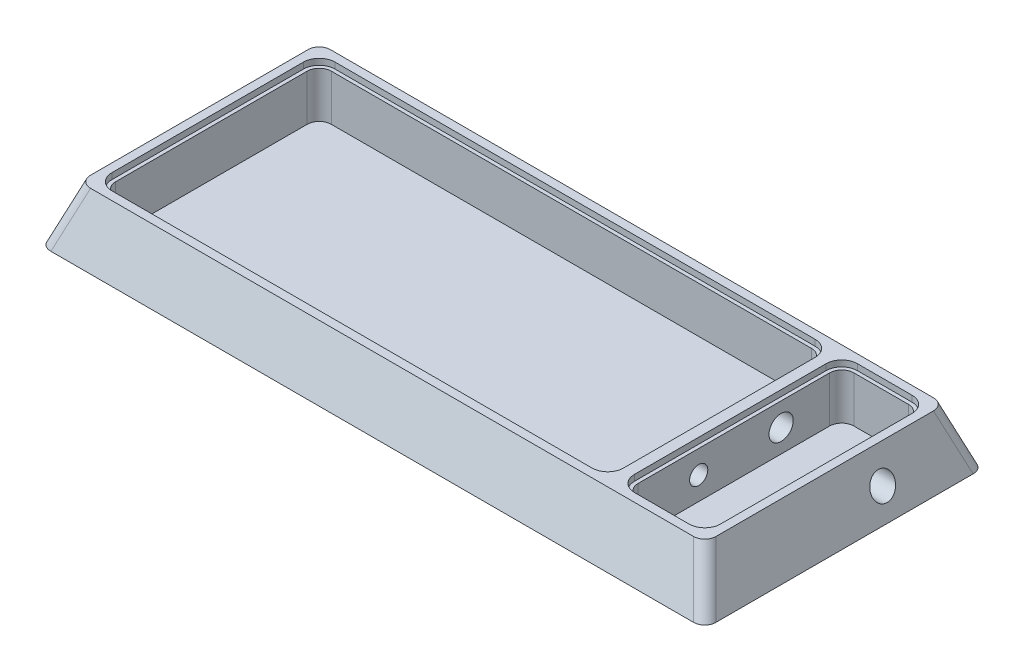
SolidWorks part; units mm, degrees
ref_plane "Front Plane" through (0, 0, 0) normal (0, 0, 1) x (1, 0, 0)
ref_plane "Top Plane" through (0, 0, 0) normal (0, 1, 0) x (1, 0, 0)
ref_plane "Right Plane" through (0, 0, 0) normal (1, 0, 0) x (0, 0, -1)
sketch "Sketch2" plane through (0, 0, 0) normal (0, 1, 0) x (1, 0, 0)
  line L0 (168, -89) -> (168, 89)
  line L1 (-248, -89) -> (168, -89)
  line L2 (-248, -89) -> (-248, 89)
  line L3 (-248, 89) -> (168, 89)
  line L4 (248, -89) -> (248, 89)
  line L5 (-248, -89) -> (248, 89) construction
  line L6 (-248, 89) -> (248, -89) construction
  line L7 (-238, -79) -> (138, -79)
  line L8 (-238, -79) -> (-238, -11)
  line L9 (-238, -11) -> (138, -11)
  line L10 (138, -79) -> (138, -11)
  line L11 (-238, 4) -> (112, 4)
  line L12 (-238, 4) -> (-238, 84)
  line L13 (-238, 84) -> (112, 84)
  line L14 (112, 4) -> (112, 84)
  line L15 (-258, 99) -> (258, 99)
  line L16 (258, -99) -> (258, 99)
  line L17 (-258, -99) -> (258, -99)
  line L18 (-258, -99) -> (-258, 99)
  line L19 (183, -89) -> (183, 89)
  line L20 (183, 89) -> (248, 89)
  line L21 (-248, 89) -> (248, 89) construction
  line L22 (183, -89) -> (248, -89)
  line L23 (-248, -89) -> (248, -89) construction
  point P0 (0, 0)
  point P14 (-238, -45)
  point P15 (-238, 44)
  dimension "D1" = 178
  dimension "D3" = 376
  dimension "D4" = 68
  dimension "D5" = 350
  dimension "D6" = 80
  dimension "D7" = 10
  dimension "D8" = 10
  dimension "D9" = 15
  dimension "D2" = 416
  dimension "D10" = 80
  dimension "D11" = 10
  dimension "D12" = 15
extrude "Boss-Extrude2" add sketch "Sketch2" along normal blind 45 contours L18 L17 L16 L15 L22 L19 L20 L4 L2 L3 L0 L1 region at (0, 0, -93.4732)
draft "Draft3" type of draft neutral plane draft angle 20 faces to draft 4 face at (0, 22.5, -99) face at (258, 22.5, 0) face at (0, 22.5, 99) face at (-258, 22.5, 0) neutral plane through (0, 45, 0) neutral plane normal (0, 1, 0) parameters "D1"=20
fillet "Fillet1" radius 10 12 edges at (-248, 22.5, 89) (168, 22.5, 89) (168, 22.5, -89) (-248, 22.5, -89) (-266.1893, 22.5, -107.1893) (266.1893, 22.5, -107.1893) (266.1893, 22.5, 107.1893) (248, 22.5, 89) (248, 22.5, -89) (183, 22.5, -89) (183, 22.5, 89) (-266.1893, 22.5, 107.1893)
extrude "Boss-Extrude3" add sketch "Sketch2<3>" along normal blind 2 contours L3 L2 L1 L0 L14 L11 L12 L13 L10 L7 L8 L9 | L7 L10 L9 L8 | L11 L14 L13 L12 | L19 L22 L4 L20 region at (3.9297, 0, 3.9766) region at (215.5, 0, 0) region at (-50, 0, 45) region at (-63, 0, -44)
sketch "Sketch2<3>" plane through (0, 0, 0) normal (0, 1, 0) x (1, 0, 0) same geometry as "Sketch2"
sketch "Sketch3" plane through (0, 45, 0) normal (0, 1, 0) x (1, 0, 0)
  line L12 (171, -79) -> (171, 79)
  line L13 (-238, -92) -> (158, -92)
  line L14 (-251, 79) -> (-251, -79)
  line L15 (158, 92) -> (-238, 92)
  line L16 (171, -79) -> (171, 79)
  line L17 (-238, -92) -> (158, -92)
  line L18 (-251, 79) -> (-251, -79)
  line L19 (158, 92) -> (-238, 92)
  line L24 (193, -92) -> (238, -92)
  line L25 (180, 79) -> (180, -79)
  line L26 (238, 92) -> (193, 92)
  line L27 (251, -79) -> (251, 79)
  line L28 (193, -92) -> (238, -92)
  line L29 (180, 79) -> (180, -79)
  line L30 (238, 92) -> (193, 92)
  line L31 (251, -79) -> (251, 79)
  arc A8 (158, -92) -> (171, -79) centre (158, -79) ccw
  arc A9 (171, 79) -> (158, 92) centre (158, 79) ccw
  arc A10 (-251, -79) -> (-238, -92) centre (-238, -79) ccw
  arc A11 (-238, 92) -> (-251, 79) centre (-238, 79) ccw
  arc A12 (158, -92) -> (171, -79) centre (158, -79) ccw
  arc A13 (171, 79) -> (158, 92) centre (158, 79) ccw
  arc A14 (-251, -79) -> (-238, -92) centre (-238, -79) ccw
  arc A15 (-238, 92) -> (-251, 79) centre (-238, 79) ccw
  arc A20 (180, -79) -> (193, -92) centre (193, -79) ccw
  arc A21 (193, 92) -> (180, 79) centre (193, 79) ccw
  arc A22 (251, 79) -> (238, 92) centre (238, 79) ccw
  arc A23 (238, -92) -> (251, -79) centre (238, -79) ccw
  arc A24 (180, -79) -> (193, -92) centre (193, -79) ccw
  arc A25 (193, 92) -> (180, 79) centre (193, 79) ccw
  arc A26 (251, 79) -> (238, 92) centre (238, 79) ccw
  arc A27 (238, -92) -> (251, -79) centre (238, -79) ccw
  dimension "D1" = 3
  dimension "D2" = 3
extrude "Cut-Extrude1" cut sketch "Sketch3" against normal blind 5
sketch "Sketch4" plane through (248, 0, 0) normal (-1, 0, 0) x (0, 0, 1)
  line L0 (-79, 40) -> (-79, 2) construction
  circle A0 centre (-39, 21) radius 10
  point P4 (-79, 21)
  dimension "D1" = 20
  dimension "D2" = 40
extrude "Cut-Extrude2" cut sketch "Sketch4" along normal up to surface (80 mm away) and the other way blind 54 from offset 0 up to face at (168, 21, 0)
sketch "Sketch5" plane through (183, 0, 0) normal (1, 0, 0) x (0, 0, -1)
  line L0 (-79, 40) -> (-79, 2) construction
  circle A0 centre (-29, 21) radius 7.5
  point P4 (-79, 21)
  dimension "D1" = 15
  dimension "D2" = 50
extrude "Cut-Extrude3" cut sketch "Sketch5" against normal up to surface (15 mm away) up to face at (168, 21, -29)
equation "\"D1@Sketch2\"=\"D8@Sketch2\"+\"D4@Sketch2\"+\"D9@Sketch2\"+\"D6@Sketch2\"+5"
equation "\"D2@Sketch2\"=\"D7@Sketch2\"+\"D3@Sketch2\"+30"
